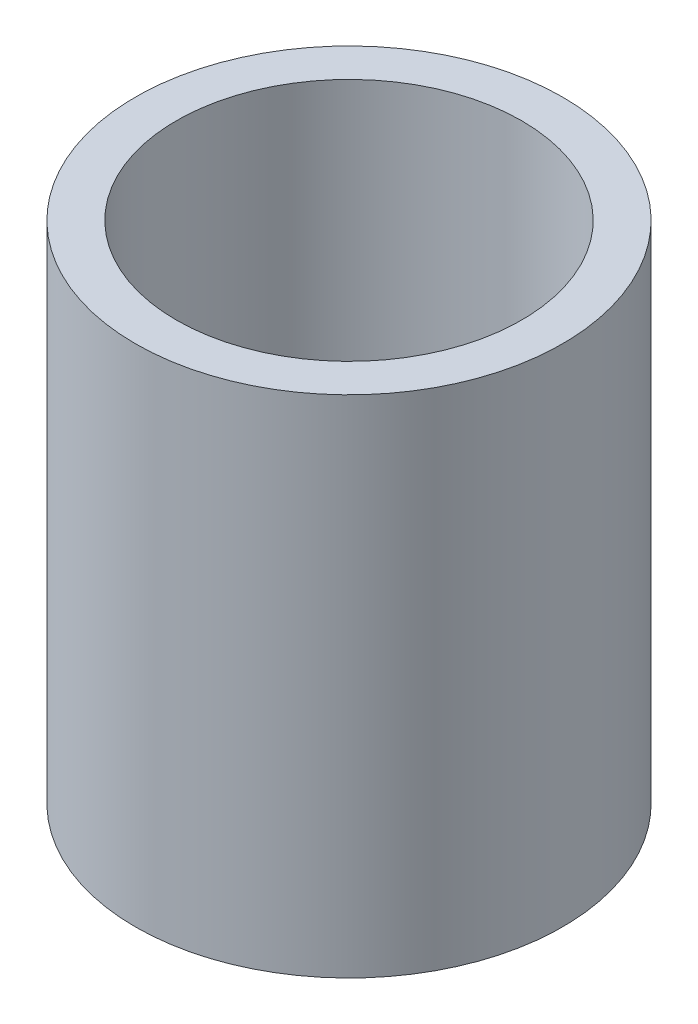
SolidWorks part; units mm, degrees
ref_plane "Front Plane" through (0, 0, 0) normal (0, 0, 1) x (1, 0, 0)
ref_plane "Top Plane" through (0, 0, 0) normal (0, 1, 0) x (1, 0, 0)
ref_plane "Right Plane" through (0, 0, 0) normal (1, 0, 0) x (0, 0, -1)
sketch "Sketch1" plane through (0, 0, 0) normal (0, 1, 0) x (1, 0, 0)
  circle A0 centre (0, 0) radius 6.325
  circle A1 centre (0, 0) radius 7.825
  point P6 (4.915, 0.3052)
  dimension "D1" = 1.5
  dimension "D2" = 12.65
extrude "Boss-Extrude1" add sketch "Sketch1" along normal blind 12.75
extrude "Boss-Extrude2" add sketch "Sketch1<2>" against normal blind 5.75 contours A1
sketch "Sketch1<2>" plane through (0, 0, 0) normal (0, 1, 0) x (1, 0, 0) same geometry as "Sketch1"
sketch "Sketch2" plane through (0, -5.75, 0) normal (0, -1, 0) x (1, 0, 0)
  line L7 (-2.0058, -1.45) -> (2.0058, -1.45)
  line L8 (-2.0058, -1.45) -> (-2.0058, 1.45)
  line L9 (-2.0058, 1.45) -> (2.0058, 1.45)
  line L10 (2.0058, -1.45) -> (2.0058, 1.45)
  arc A2 (2.0058, 1.45) -> (2.0058, -1.45) centre (0, 0) cw
  arc A3 (-2.0058, 1.45) -> (-2.0058, -1.45) centre (0, 0) ccw
extrude "Cut-Extrude2" cut sketch "Sketch2" against normal blind 5.75 contours L7 L10 L9 L8 | L8 A3 | A2 L10 region at (0, -5.75, 0) region at (-2.1951, -5.75, 0) region at (2.1951, -5.75, 0)
